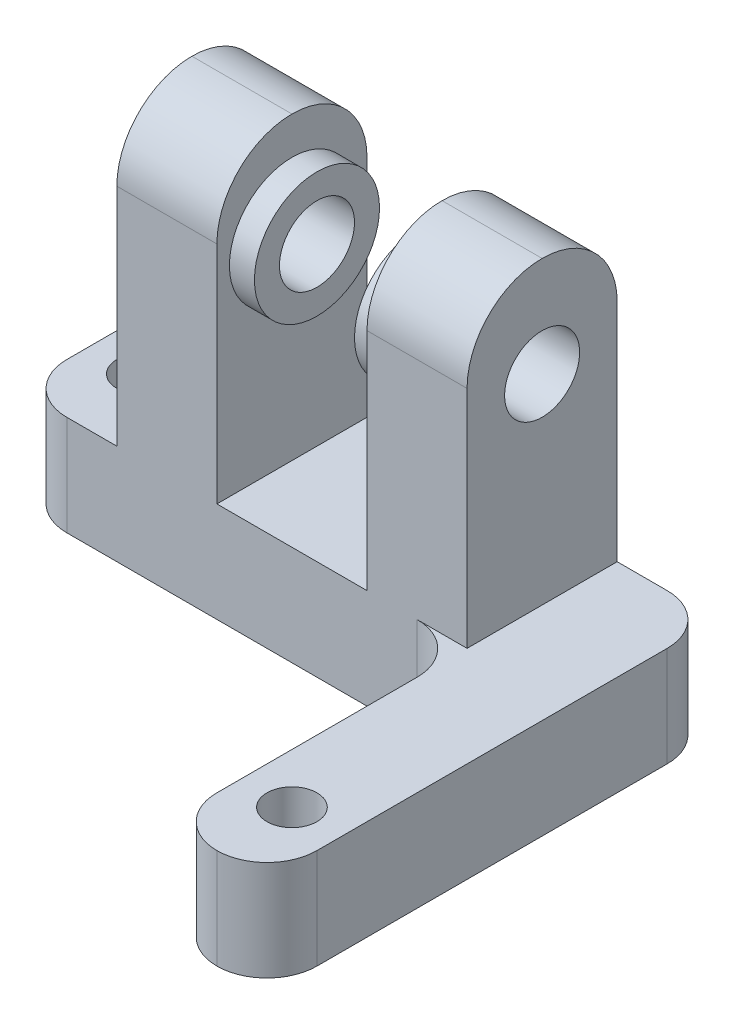
SolidWorks part; units mm, degrees
ref_plane "Front Plane" through (0, 0, 0) normal (0, 0, 1) x (1, 0, 0)
ref_plane "Top Plane" through (0, 0, 0) normal (0, 1, 0) x (1, 0, 0)
ref_plane "Right Plane" through (0, 0, 0) normal (1, 0, 0) x (0, 0, -1)
sketch "Sketch2" plane through (0, 0, 0) normal (0, 1, 0) x (1, 0, 0)
  line L1 (-7, 3) -> (7, 3)
  line L2 (-7, 3) -> (-7, -3)
  line L3 (-7, -3) -> (7, -3)
  line L4 (7, 3) -> (7, -3)
  line L5 (-7, 3) -> (7, -3) construction
  line L6 (-7, -3) -> (7, 3) construction
  point P0 (0, 0)
extrude "Boss-Extrude1" add sketch "Sketch2" along normal blind 4
sketch "Sketch3" plane through (0, 4, 0) normal (0, 1, 0) x (1, 0, 0)
  line L0 (-7, -3) -> (-3, -3)
  line L1 (-7, -3) -> (7, -3) construction
  line L2 (-3, -3) -> (-3, 3)
  line L3 (7, 3) -> (-7, 3) construction
  line L4 (-3, 3) -> (-7, 3)
  line L5 (-7, 3) -> (-7, -3)
  line L6 (7, -3) -> (3, -3)
  line L7 (3, -3) -> (3, 3)
  line L8 (3, 3) -> (7, 3)
  line L9 (7, 3) -> (7, -3)
extrude "Boss-Extrude2" add sketch "Sketch3" along normal blind 12
sketch "Sketch4" plane through (7, 0, 0) normal (1, 0, 0) x (0, 0, -1)
  circle A0 centre (0, 12) radius 1.5
extrude "Cut-Extrude1" cut sketch "Sketch4" against normal through all both and the other way through all
sketch "Sketch5" plane through (-3, 0, 0) normal (1, 0, 0) x (0, 0, -1)
  circle A0 centre (0, 12) radius 1.5
  circle A1 centre (0, 12) radius 2.5
extrude "Boss-Extrude3" add sketch "Sketch5" along normal blind 1
sketch "Sketch6" plane through (3, 0, 0) normal (-1, 0, 0) x (0, 0, 1)
  circle A0 centre (0, 12) radius 1.5
  circle A1 centre (0, 12) radius 2.5
extrude "Boss-Extrude4" add sketch "Sketch6" along normal blind 1
sketch "Sketch7" plane through (0, 4, 0) normal (0, 1, 0) x (1, 0, 0)
  line L2 (11, 3) -> (11, -3)
  line L4 (-7, -3) -> (-7, 3)
  line L5 (-7, 3) -> (-7, -3) construction
  line L6 (-7, 3) -> (-11, 3)
  line L7 (-11, 3) -> (-11, -3)
  line L8 (-11, -3) -> (-7, -3)
  line L9 (11, 3) -> (7, 3)
  line L10 (7, 3) -> (7, -3)
  line L11 (11, -3) -> (11, -11)
  line L13 (7, -11) -> (7, -3)
  line L14 (11, -11) -> (11, -15)
  line L15 (11, -15) -> (7, -15)
  line L16 (7, -15) -> (7, -11)
  circle A0 centre (9, -12) radius 1
  circle A1 centre (-9, 0) radius 1
extrude "Boss-Extrude5" add sketch "Sketch7" against normal blind 4
fillet "Fillet1" radius 2 6 edges at (-11, 2, -3) (11, 2, -3) (-11, 2, 3) (7, 2, 3) (11, 2, 15) (7, 2, 15)
fillet "Fillet2" radius 3 4 edges at (-5, 16, -3) (5, 16, -3) (5, 16, 3) (-5, 16, 3)
